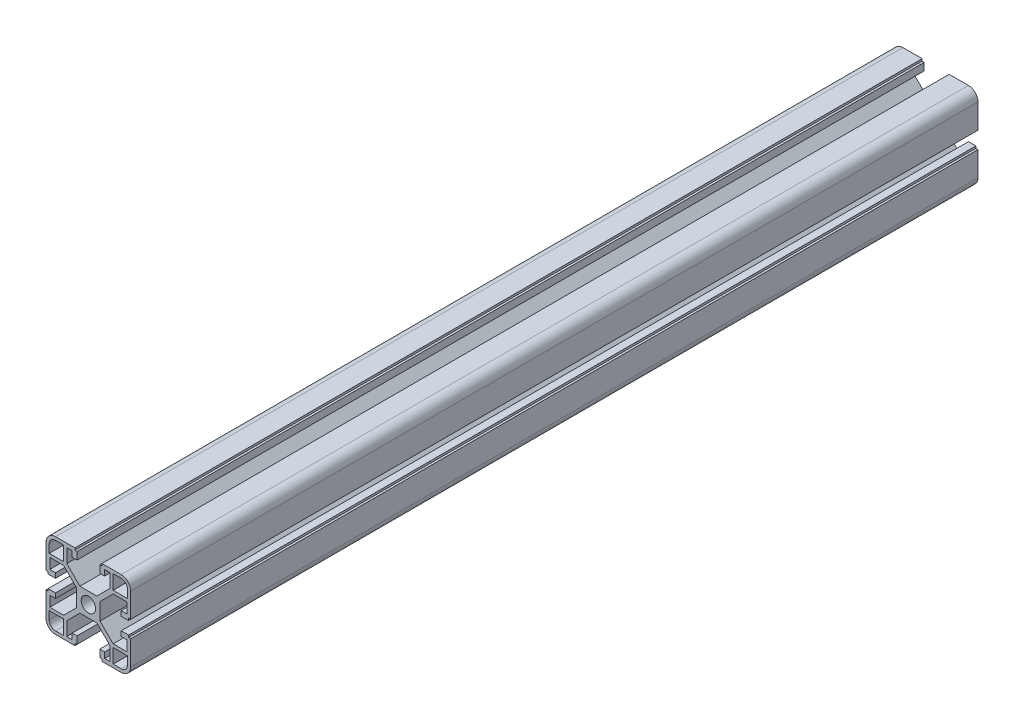
SolidWorks part; units mm, degrees
material "6061-T6 (SS)"
ref_plane "Front Plane" through (0, 0, 0) normal (0, 0, 1) x (1, 0, 0)
ref_plane "Top Plane" through (0, 0, 0) normal (0, 1, 0) x (1, 0, 0)
ref_plane "Right Plane" through (0, 0, 0) normal (1, 0, 0) x (0, 0, -1)
sketch "Sketch1" plane through (0, 0, 0) normal (0, 0, 1) x (1, 0, 0)
  line L0 (3.4, 0) -> (5.5, 0)
  line L1 (10.19, 11.69) -> (4, 5.5)
  line L2 (11.69, 10.19) -> (5.5, 4)
  line L3 (18.2, 10.19) -> (11.69, 10.19)
  line L4 (18.2, 10.19) -> (18.2, 5.2656)
  line L5 (18.2, 5.2656) -> (15.5, 5.2656)
  line L6 (15.5, 5.2656) -> (15.5, 2.9656)
  line L7 (15.5, 2.9656) -> (19, 2.9656)
  line L8 (19, 2.9656) -> (19, 3.9656)
  line L9 (19, 3.9656) -> (20, 3.9656)
  line L10 (20, 3.9656) -> (20, 15.5)
  line L11 (15.5, 20) -> (6.3853, 20)
  line L12 (18.5, 11.69) -> (18.5, 15.5)
  line L13 (15.5, 18.5) -> (11.69, 18.5)
  line L14 (11.69, 11.69) -> (11.69, 18.5)
  line L15 (0, 3.4) -> (0, 5.5)
  line L16 (4, 5.5) -> (0, 5.5)
  line L17 (6.3853, 20) -> (6.3853, 19)
  line L18 (5.5, 0) -> (5.5, 4)
  line L19 (6.3853, 19) -> (5.3853, 19)
  line L20 (5.3853, 19) -> (5.3853, 15.5)
  line L21 (5.3853, 15.5) -> (7.6853, 15.5)
  line L22 (10.19, 11.69) -> (10.19, 18.2)
  line L23 (11.69, 11.69) -> (18.5, 11.69)
  line L24 (7.6853, 18.2) -> (7.6853, 15.5)
  line L25 (10.19, 18.2) -> (7.6853, 18.2)
  arc A0 (20, 15.5) -> (15.5, 20) centre (15.5, 15.5) ccw
  arc A1 (18.5, 15.5) -> (15.5, 18.5) centre (15.5, 15.5) ccw
  arc A2 (3.4, 0) -> (0, 3.4) centre (0, 0) ccw
  dimension "D3" = 4.5
  dimension "D18" = 1.5
  dimension "D9" = 3.4
  dimension "D20" = 1.8
  dimension "D25" = 3
  dimension "D1" = 5.5
  dimension "D2" = 1.5
  dimension "D4" = 14.5
  dimension "D5" = 1.5
  dimension "D6" = 2.1
  dimension "D7" = 2.3
  dimension "D8" = 1.8
  dimension "D10" = 6.81
  dimension "D11" = 2.1
  dimension "D12" = 1
  dimension "D13" = 4.5
  dimension "D14" = 45
  dimension "D15" = 14.5
  dimension "D16" = 1
  dimension "D17" = 1.5
  dimension "D19" = 6.81
  dimension "D21" = 4.5
  dimension "D22" = 2.3
  dimension "D23" = 1
  dimension "D24" = 1
  dimension "D26" = 8.754
  dimension "D27" = 8.754
  dimension "D28" = 4.9244
  dimension "D29" = 2.5047
extrude "Boss-Extrude1" add sketch "Sketch1" along normal blind 400
mirror "Mirror1" about plane through (0, 0, 0) normal (0, 1, 0) of "Boss-Extrude1"
mirror "Mirror2" about plane through (0, 0, 0) normal (1, 0, 0) of "Boss-Extrude1"
mirror "Mirror3" about plane through (0, 0, 0) normal (0, 1, 0) of "Mirror2"
sketch "Croquis2" plane through (0, 0, 400) normal (0, 0, 1) x (1, 0, 0)
  line L0 (4, 5.5) -> (5.5, 4)
  line L1 (5.5, 4) -> (5.5, -4)
  line L2 (5.5, -4) -> (4, -5.5)
  line L3 (4, -5.5) -> (4, -23.2335)
  line L4 (4, -23.2335) -> (29.7306, -23.2335)
  line L5 (29.7306, -23.2335) -> (29.7306, 32.1268)
  line L6 (29.7306, 32.1268) -> (4, 32.1268)
  line L7 (4, 32.1268) -> (4, 5.5)
extrude "Cortar-Extruir2" [suppressed] cut sketch "Croquis2" against normal blind 70
